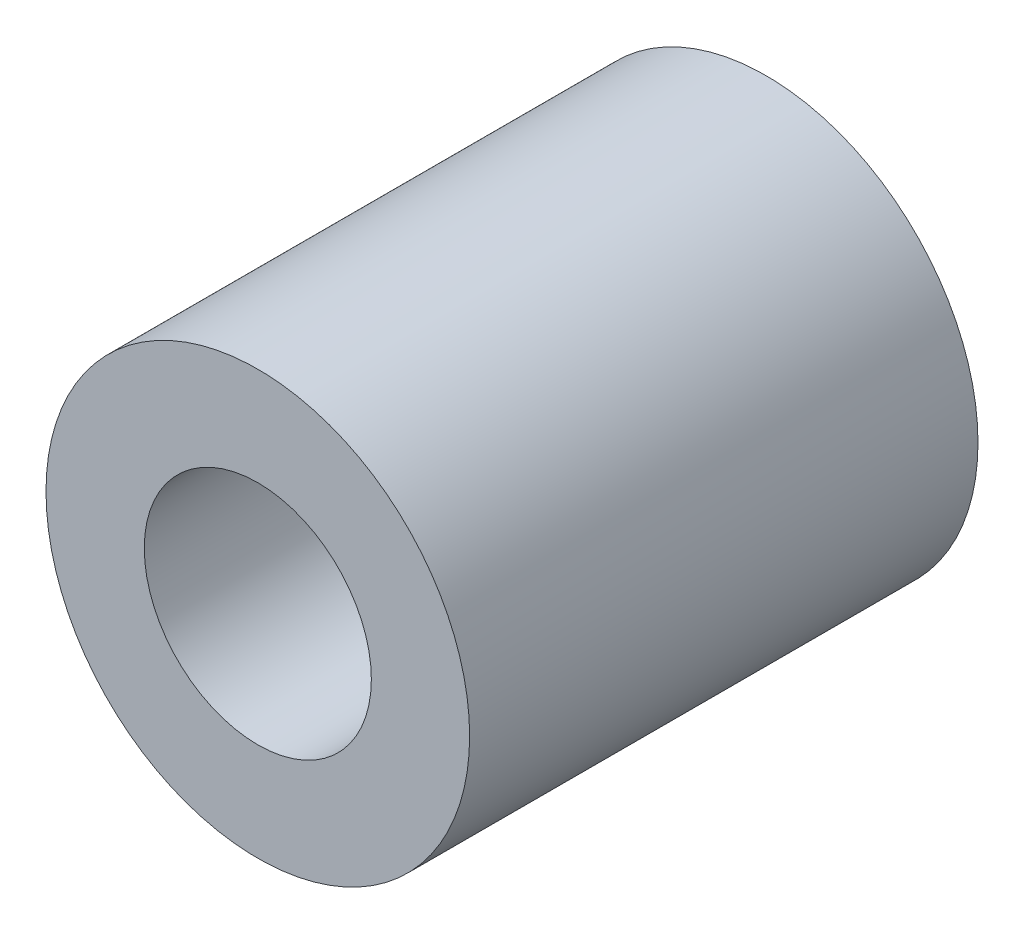
SolidWorks part; units mm, degrees
ref_plane "Front Plane" through (0, 0, 0) normal (0, 0, 1) x (1, 0, 0)
ref_plane "Top Plane" through (0, 0, 0) normal (0, 1, 0) x (1, 0, 0)
ref_plane "Right Plane" through (0, 0, 0) normal (1, 0, 0) x (0, 0, -1)
sketch "Sketch1" plane through (0, 0, 0) normal (0, 0, 1) x (1, 0, 0)
  circle A0 centre (0, 0) radius 4.7625
  circle A1 centre (0, 0) radius 2.5527
  point P3 (0, 0)
  dimension "D1" = 9.525
  dimension "D2" = 5.1054
extrude "Boss-Extrude1" add sketch "Sketch1" along normal blind 11.43
